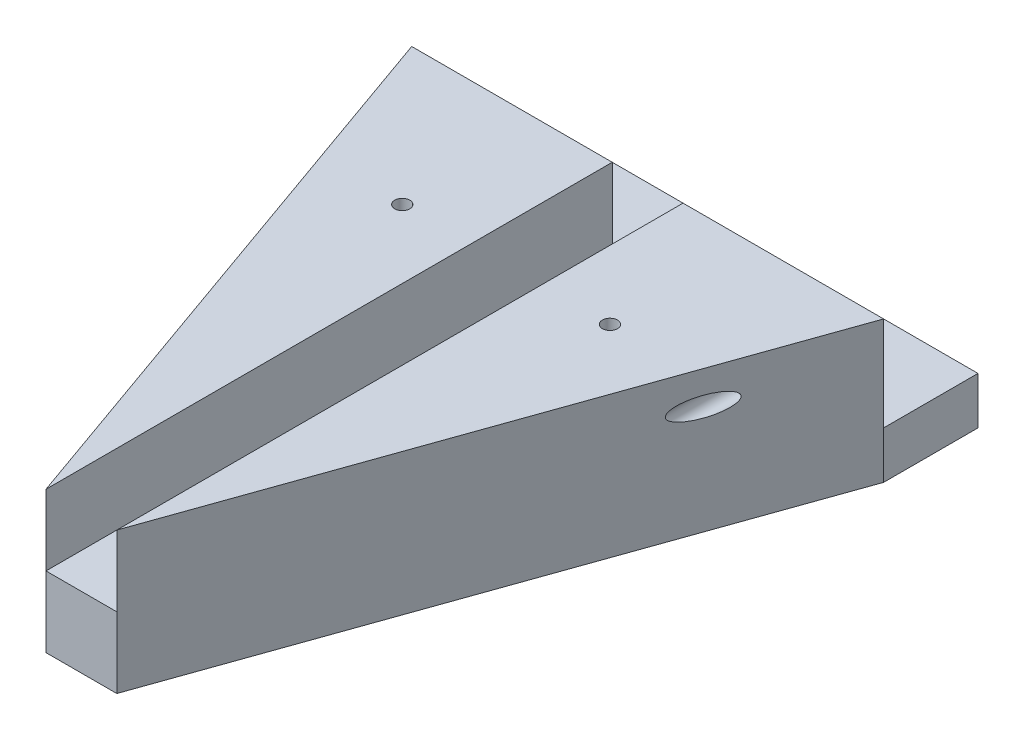
SolidWorks part; units mm, degrees
ref_plane "前视基准面" through (0, 0, 0) normal (0, 0, 1) x (1, 0, 0)
ref_plane "上视基准面" through (0, 0, 0) normal (0, 1, 0) x (1, 0, 0)
ref_plane "右视基准面" through (0, 0, 0) normal (1, 0, 0) x (0, 0, -1)
sketch "草图1" plane through (0, 0, 0) normal (0, 1, 0) x (1, 0, 0)
  line L0 (0, 0) -> (0, -94.6857) construction
  line L1 (-50, -10) -> (50, -10)
  line L2 (-50, -10) -> (-50, 10)
  line L3 (-50, 10) -> (50, 10)
  line L4 (50, -10) -> (50, 10)
  line L5 (-50, -10) -> (50, 10) construction
  line L6 (-50, 10) -> (50, -10) construction
  line L7 (-50, -10) -> (-7.5, -130)
  line L8 (-7.5, -130) -> (7.5, -130)
  line L9 (-7.5, -130) -> (-7.5, -10)
  line L10 (-7.5, -10) -> (7.5, -10)
  line L11 (7.5, -130) -> (7.5, -10)
  line L12 (-7.5, -130) -> (7.5, -10) construction
  line L13 (-7.5, -10) -> (7.5, -130) construction
  line L14 (7.5, -130) -> (50, -10)
  point P0 (0, 0)
  point P8 (0, -70)
  dimension "D1" = 20
  dimension "D2" = 100
  dimension "D3" = 15
  dimension "D4" = 120
extrude "凸台-拉伸1" add sketch "草图1" along normal blind 10 contours L7 L9 L1 | L1 L4 L3 L2 | L8 L11 L1 L9 | L11 L14 L1 region at (0, 0, 0) region at (-21.6667, 0, 50) region at (0, 0, 70) region at (21.6667, 0, 50)
extrude "凸台-拉伸2" add sketch "草图1<3>" along normal blind 15 contours L7 L9 L1 | L8 L11 L1 L9 | L11 L14 L1 region at (-21.6667, 0, 50) region at (0, 0, 70) region at (21.6667, 0, 50)
sketch "草图1<3>" plane through (0, 0, 0) normal (0, 1, 0) x (1, 0, 0) same geometry as "草图1"
sketch "草图2" plane through (0, 10, 0) normal (0, 1, 0) x (1, 0, 0)
  line L0 (0, 23.978) -> (0, -41.3835) construction
  circle A0 centre (20, 0) radius 1.6
  circle A1 centre (-20, 0) radius 1.6
  dimension "D1" = 3.2
  dimension "D2" = 3.2
  dimension "D3" = 20
  dimension "D4" = 20
extrude "切除-拉伸1" cut sketch "草图2" against normal blind 15
extrude "凸台-拉伸3" add sketch "草图1<4>" along normal blind 20 from offset 10 contours L7 L9 L1 | L11 L14 L1 region at (-21.6667, 0, 50) region at (21.6667, 0, 50)
sketch "草图1<4>" plane through (0, 0, 0) normal (0, 1, 0) x (1, 0, 0) same geometry as "草图1"
sketch "草图5" plane through (0, 30, 0) normal (0, 1, 0) x (1, 0, 0)
  line L0 (0, 0) -> (0, -135.6589) construction
  line L1 (-22, -40) -> (22, -40) construction
  line L2 (50, -10) -> (-50, -10) construction
  circle A0 centre (22, -40) radius 1.6
  circle A1 centre (-22, -40) radius 1.6
  dimension "D3" = 30
  dimension "D4" = 3.2
  dimension "D5" = 3.2
  dimension "D1" = 22
  dimension "D2" = 22
extrude "切除-拉伸4" cut sketch "草图5" against normal blind 100
sketch "草图6" plane through (0, 0, 10) normal (0, 0, -1) x (-1, 0, 0)
  line L0 (-69.3816, 23) -> (67.782, 23) construction
  line L1 (0, 43.943) -> (0, -11.6423) construction
  line L2 (50, 30) -> (7.5, 30) construction
  circle A0 centre (40, 23) radius 1.6
  circle A1 centre (-40, 23) radius 1.6
  dimension "D4" = 3.2
  dimension "D5" = 3.2
  dimension "D1" = 7
  dimension "D2" = 40
  dimension "D3" = 40
extrude "切除-拉伸5" cut sketch "草图6" against normal blind 100
sketch "草图7" plane through (0, 0, 10) normal (0, 0, -1) x (-1, 0, 0)
  circle A0 centre (-40, 23) radius 2.1
  circle A1 centre (40, 23) radius 2.1
  dimension "D1" = 4.2
  dimension "D2" = 4.2
extrude "切除-拉伸6" cut sketch "草图7" against normal blind 100 from offset 20 offset against normal yes
